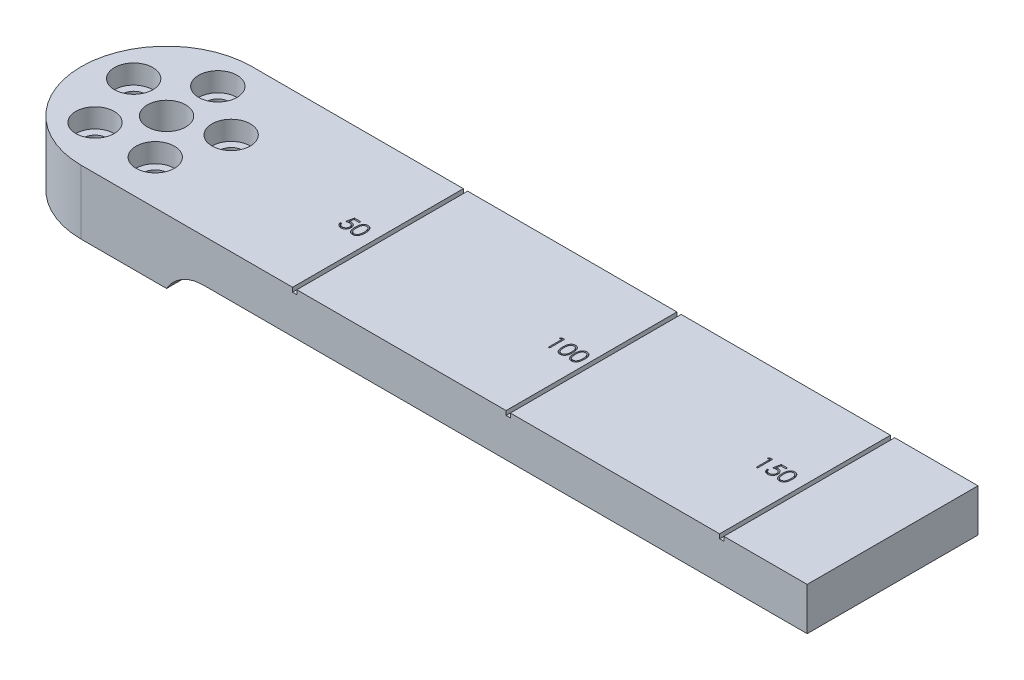
SolidWorks part; units mm, degrees
ref_plane "Front Plane" through (0, 0, 0) normal (0, 0, 1) x (1, 0, 0)
ref_plane "Top Plane" through (0, 0, 0) normal (0, 1, 0) x (1, 0, 0)
ref_plane "Right Plane" through (0, 0, 0) normal (1, 0, 0) x (0, 0, -1)
sketch "Sketch1" plane through (0, 0, 0) normal (0, 1, 0) x (1, 0, 0)
  line L0 (0, 20) -> (170, 20)
  line L1 (170, 20) -> (170, -20)
  line L2 (170, -20) -> (0, -20)
  arc A0 (0, 20) -> (0, -20) centre (0, 0) ccw
  dimension "D1" = 40
  dimension "D2" = 170
extrude "Boss-Extrude1" add sketch "Sketch1" along normal blind 15
sketch "Sketch2" plane through (0, 15, 0) normal (0, 1, 0) x (1, 0, 0)
  circle A0 centre (0, 0) radius 12 construction
  circle A1 centre (0, 12) radius 4.5
  circle A2 centre (11.4127, 3.7082) radius 4.5
  circle A3 centre (7.0534, -9.7082) radius 4.5
  circle A4 centre (-7.0534, -9.7082) radius 4.5
  circle A5 centre (-11.4127, 3.7082) radius 4.5
  point P6 (13.9904, 4.2857)
  point P7 (0, 0)
  point P15 (0, 0)
  dimension "D1" = 24
  dimension "D2" = 9
  dimension "D3" = 5
extrude "Cut-Extrude1" cut sketch "Sketch2" against normal blind 4.5
sketch "Sketch3" plane through (0, 10.5, 0) normal (0, 1, 0) x (1, 0, 0)
  circle A0 centre (0, 12) radius 2.75
  circle A1 centre (11.4127, 3.7082) radius 2.75
  circle A2 centre (7.0534, -9.7082) radius 2.75
  circle A3 centre (-7.0534, -9.7082) radius 2.75
  circle A4 centre (-11.4127, 3.7082) radius 2.75
  point P4 (15.7768, 2.6109)
  point P5 (0, 0)
  point P13 (0, 0)
  point P15 (0, 0)
  dimension "D1" = 5.5
  dimension "D2" = 5
extrude "Cut-Extrude2" cut sketch "Sketch3" against normal through all
sketch "Sketch4" plane through (0, 15, 0) normal (0, 1, 0) x (1, 0, 0)
  circle A0 centre (0, 0) radius 4.5
  dimension "D1" = 9
extrude "Cut-Extrude3" cut sketch "Sketch4" against normal through all
sketch "Sketch5" plane through (0, 15, 0) normal (0, 1, 0) x (1, 0, 0)
  line L0 (49.5, 20) -> (49.5, -20)
  line L1 (170, 20) -> (0, 20) construction
  line L2 (0, -20) -> (170, -20) construction
  line L3 (49.5, -20) -> (50.5, -20)
  line L4 (50.5, -20) -> (50.5, 20)
  line L5 (50.5, 20) -> (49.5, 20)
  line L6 (99.5, 20) -> (99.5, -20)
  line L7 (99.5, -20) -> (100.5, -20)
  line L8 (100.5, -20) -> (100.5, 20)
  line L9 (100.5, 20) -> (99.5, 20)
  line L10 (149.5, 20) -> (149.5, -20)
  line L11 (149.5, -20) -> (150.5, -20)
  line L12 (150.5, -20) -> (150.5, 20)
  line L13 (150.5, 20) -> (149.5, 20)
  text T0 "50"
  text T1 "150\r\n"
  text T2 "100"
  point P16 (98.8504, 20)
  point P17 (102.4508, -20)
  point P18 (96.5896, -20)
  point P19 (124.8073, -20)
  point P20 (128.659, -20)
  point P21 (124.1375, 20)
  point P26 (0, 0)
  point P27 (89.9457, -2.6479)
  point P28 (139.0728, -2.0959)
  point P29 (41.8123, -1.3232)
  point P30 (90.3873, -2.2063)
  dimension "D1" = 49.5
  dimension "D2" = 1
  dimension "D3" = 99.5
  dimension "D4" = 1
  dimension "D5" = 149.5
  dimension "D6" = 1
extrude "Cut-Extrude4" cut sketch "Sketch5" against normal blind 1
sketch "Sketch6" plane through (170, 0, 0) normal (1, 0, 0) x (0, 0, -1)
  line L1 (-20, 0) -> (20, 0)
  line L2 (-20, 0) -> (-20, 5)
  line L3 (-20, 5) -> (20, 5)
  line L4 (20, 0) -> (20, 5)
  dimension "D1" = 5
extrude "Cut-Extrude5" cut sketch "Sketch6" against normal blind 150
fillet "Fillet1" radius 10 1 edges at (20, 5, 0)
